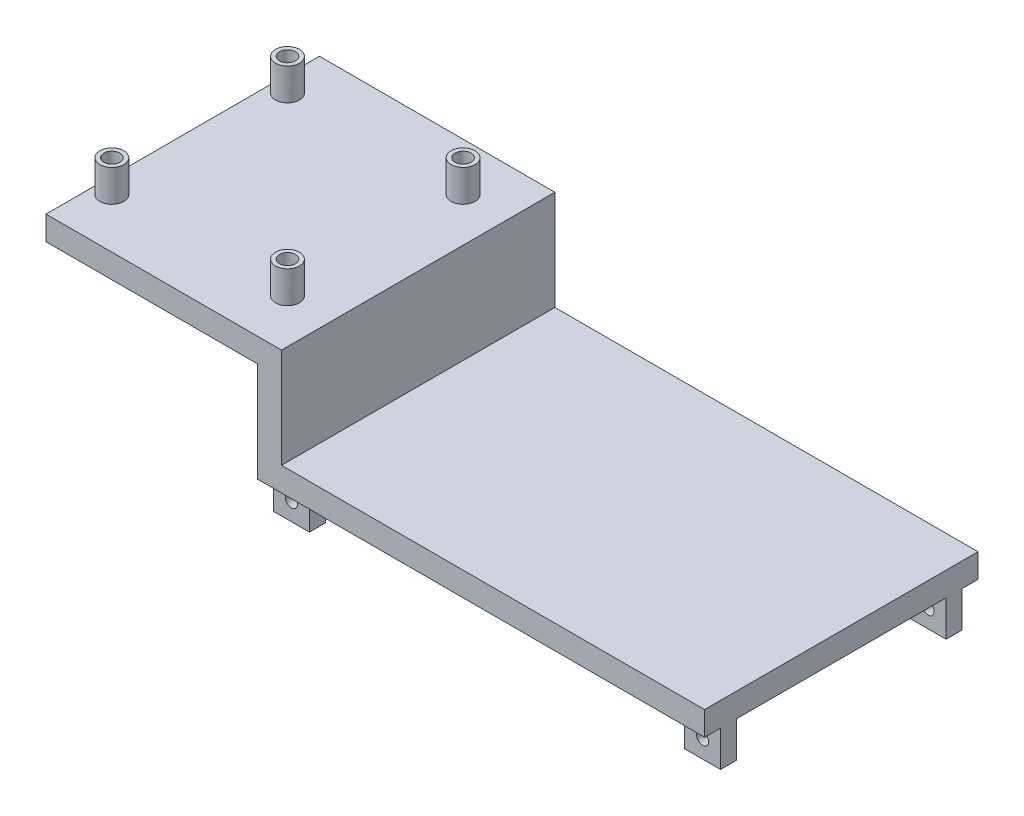
SolidWorks part; units mm, degrees
ref_plane "Front Plane" through (0, 0, 0) normal (0, 0, 1) x (1, 0, 0)
ref_plane "Top Plane" through (0, 0, 0) normal (0, 1, 0) x (1, 0, 0)
ref_plane "Right Plane" through (0, 0, 0) normal (1, 0, 0) x (0, 0, -1)
sketch "Sketch1" plane through (0, 0, 0) normal (0, 1, 0) x (1, 0, 0)
  line L1 (0, 0) -> (-112, 0)
  line L2 (0, 0) -> (0, 34.25)
  line L3 (0, 34.25) -> (-112, 34.25)
  line L4 (-112, 0) -> (-112, 34.25)
  dimension "D1" = 112
  dimension "D2" = 34.25
extrude "Boss-Extrude2" add sketch "Sketch1" along normal blind 6
sketch "Sketch3" plane through (0, 0, 0) normal (0, -1, 0) x (1, 0, 0)
  line L0 (-112, -34.25) -> (-112, 0) construction
  line L1 (-112, -4) -> (-103, -4)
  line L2 (-112, -4) -> (-112, -8)
  line L3 (-112, -8) -> (-103, -8)
  line L4 (-103, -4) -> (-103, -8)
  line L5 (0, 0) -> (0, -34.25) construction
  line L6 (0, -4) -> (-9, -4)
  line L7 (0, -4) -> (0, -8)
  line L8 (0, -8) -> (-9, -8)
  line L9 (-9, -4) -> (-9, -8)
  line L10 (-112, 0) -> (0, 0) construction
  dimension "D1" = 4
  dimension "D2" = 4
  dimension "D3" = 9
  dimension "D4" = 9
  dimension "D5" = 4
  dimension "D6" = 4
extrude "Boss-Extrude3" add sketch "Sketch3" along normal blind 9
sketch "Sketch4" plane through (0, 0, -4) normal (0, 0, 1) x (1, 0, 0)
  line L0 (-112, -9) -> (-112, 0) construction
  line L1 (-103, -9) -> (-112, -9) construction
  line L2 (0, -9) -> (-9, -9) construction
  line L3 (0, -9) -> (0, 0) construction
  circle A0 centre (-107.5, -4.5) radius 1.5
  circle A1 centre (-4.5, -4.5) radius 1.5
  dimension "D1" = 3
  dimension "D2" = 4.5
  dimension "D3" = 4.5
  dimension "D4" = 4.5
  dimension "D5" = 3
  dimension "D6" = 4.5
extrude "Cut-Extrude1" cut sketch "Sketch4" against normal through all
sketch "Sketch8" plane through (0, 6, 0) normal (0, 1, 0) x (1, 0, 0)
  line L0 (0, 34.25) -> (-112, 34.25) construction
  line L1 (-112, 0) -> (-106, 0)
  line L2 (-112, 0) -> (-112, 34.25)
  line L3 (-112, 34.25) -> (-106, 34.25)
  line L4 (-106, 0) -> (-106, 34.25)
  dimension "D1" = 6
extrude "Boss-Extrude6" add sketch "Sketch8" along normal blind 25
sketch "Sketch9" plane through (-112, 0, 0) normal (-1, 0, 0) x (0, 0, 1)
  line L0 (0, 31) -> (0, 0) construction
  line L1 (-34.25, 31) -> (0, 31)
  line L2 (-34.25, 31) -> (-34.25, 25)
  line L3 (-34.25, 25) -> (0, 25)
  line L4 (0, 31) -> (0, 25)
  dimension "D1" = 6
extrude "Boss-Extrude7" add sketch "Sketch9" along normal blind 53
mirror "Mirror2" about plane through (0, 6, -34.25) normal (0, 0, 1) of "Boss-Extrude7", "Boss-Extrude6", "Cut-Extrude1", "Boss-Extrude3", "Boss-Extrude2"
sketch "Sketch10" plane through (0, 31, 0) normal (0, 1, 0) x (1, 0, 0)
  line L0 (-165, 0) -> (-165, 68.5) construction
  line L1 (-165, 0) -> (-106, 0) construction
  circle A0 centre (-161, 12.5) radius 2
  circle A1 centre (-117, 12.5) radius 2
  circle A2 centre (-161, 56.5) radius 2
  circle A3 centre (-117, 56.5) radius 2
  dimension "D1" = 4
  dimension "D2" = 44
  dimension "D3" = 4
  dimension "D4" = 12.5
  dimension "D5" = 44
extrude "Cut-Extrude5" cut sketch "Sketch10" against normal through all and the other way blind 8
sketch "Sketch12" plane through (0, 31, 0) normal (0, 1, 0) x (1, 0, 0)
  circle A0 centre (-161, 56.5) radius 3
  circle A1 centre (-117, 56.5) radius 3
  circle A2 centre (-117, 12.5) radius 3
  circle A3 centre (-161, 12.5) radius 3
  circle A4 centre (-161, 56.5) radius 2 construction
  circle A5 centre (-117, 56.5) radius 2 construction
  circle A7 centre (-161, 12.5) radius 2 construction
  circle A8 centre (-117, 12.5) radius 2 construction
  circle A9 centre (-161, 12.5) radius 2
  circle A10 centre (-161, 56.5) radius 2
  circle A11 centre (-117, 56.5) radius 2
  circle A12 centre (-117, 12.5) radius 2
  dimension "D1" = 6
  dimension "D2" = 4
extrude "Boss-Extrude8" add sketch "Sketch12" along normal blind 8
